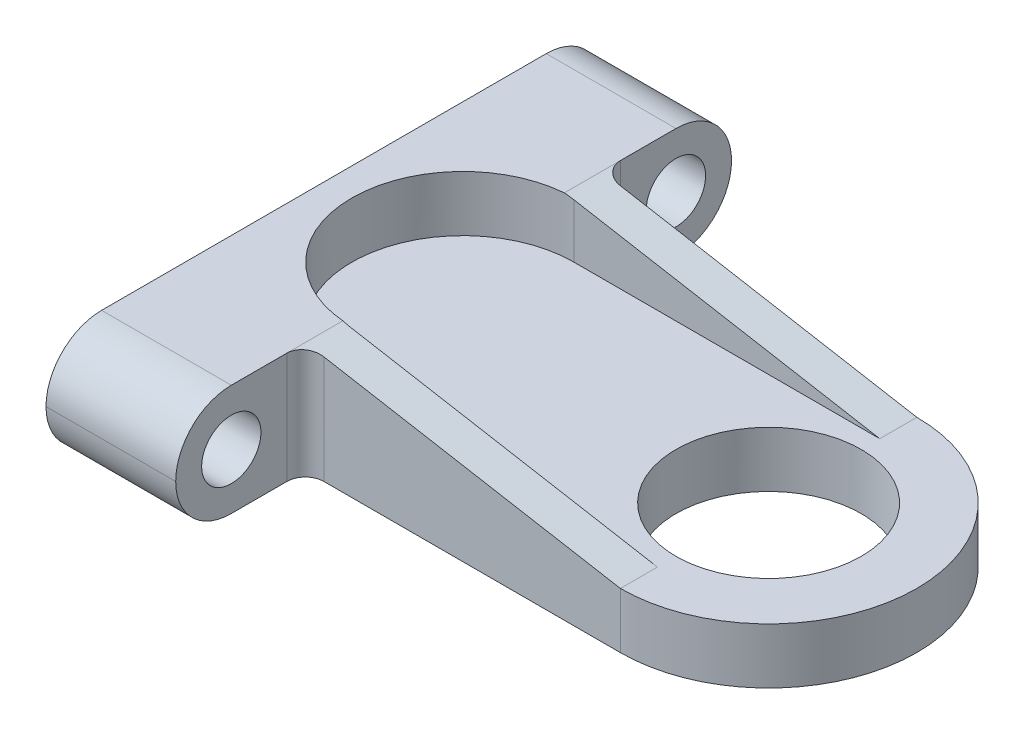
SolidWorks part; units mm, degrees
ref_plane "Front Plane" through (0, 0, 0) normal (0, 0, 1) x (1, 0, 0)
ref_plane "Top Plane" through (0, 0, 0) normal (0, 1, 0) x (1, 0, 0)
ref_plane "Right Plane" through (0, 0, 0) normal (1, 0, 0) x (0, 0, -1)
sketch "Sketch1" plane through (0, 0, 0) normal (0, 1, 0) x (1, 0, 0)
  line L0 (0, 8) -> (-17, 8)
  line L1 (-24, 15) -> (-17, 15)
  line L2 (-24, 15) -> (-24, -15)
  line L3 (-24, -15) -> (-17, -15)
  line L4 (-17, 15) -> (-17, 8)
  line L5 (0, -8) -> (-17, -8)
  line L6 (-17, -8) -> (-17, -15)
  circle A0 centre (0, 0) radius 5
  arc A1 (0, -8) -> (0, 8) centre (0, 0) ccw
  point P7 (-24, 0)
  dimension "D3" = 10
  dimension "D1" = 30
  dimension "D2" = 24
  dimension "D4" = 7
  dimension "D5" = 7
extrude "Boss-Extrude1" add sketch "Sketch1" along normal blind 6
fillet "Fillet1" radius 3 4 edges at (-20.5, 0, -15) (-20.5, 6, -15) (-20.5, 0, 15) (-20.5, 6, 15)
sketch "Sketch2" plane through (-24, 0, 0) normal (-1, 0, 0) x (0, 0, 1)
  circle A0 centre (-12, 3) radius 1.6
  circle A1 centre (12, 3) radius 1.6
  arc A2 (-12, 6) -> (-15, 3) centre (-12, 3) ccw construction
  arc A3 (15, 3) -> (12, 6) centre (12, 3) ccw construction
  dimension "D1" = 3.2
extrude "Cut-Extrude1" cut sketch "Sketch2" against normal through all
sketch "Sketch3" plane through (0, 0, 0) normal (0, 0, 1) x (1, 0, 0)
  line L0 (-17, 6) -> (8, 6)
  line L1 (8, 6) -> (8, 3)
  line L2 (8, 3) -> (0, 3)
  line L3 (0, 3) -> (-17, 6)
  line L4 (0, 6) -> (0, 0) construction
  dimension "D1" = 3
extrude "Cut-Extrude2" cut sketch "Sketch3" against normal through all and the other way through all
sketch "Sketch4" plane through (0, 3, 0) normal (0, 1, 0) x (1, 0, 0)
  line L0 (0, 0) -> (-16.5, 0) construction
  line L1 (0, -6) -> (-16.5, -6)
  line L2 (0, 6) -> (-16.5, 6)
  line L3 (-24, 12) -> (-24, -12) construction
  arc A0 (0, -6) -> (0, 6) centre (0, 0) ccw
  arc A2 (-16.5, 6) -> (-16.5, -6) centre (-16.5, 0) ccw
  point P3 (-8.25, 0)
  dimension "D1" = 12
  dimension "D2" = 1.5
extrude "Cut-Extrude3" cut sketch "Sketch4" along normal through all
fillet "Fillet3" radius 1 2 edges at (-17, 3, -8) (-17, 3, 8)
